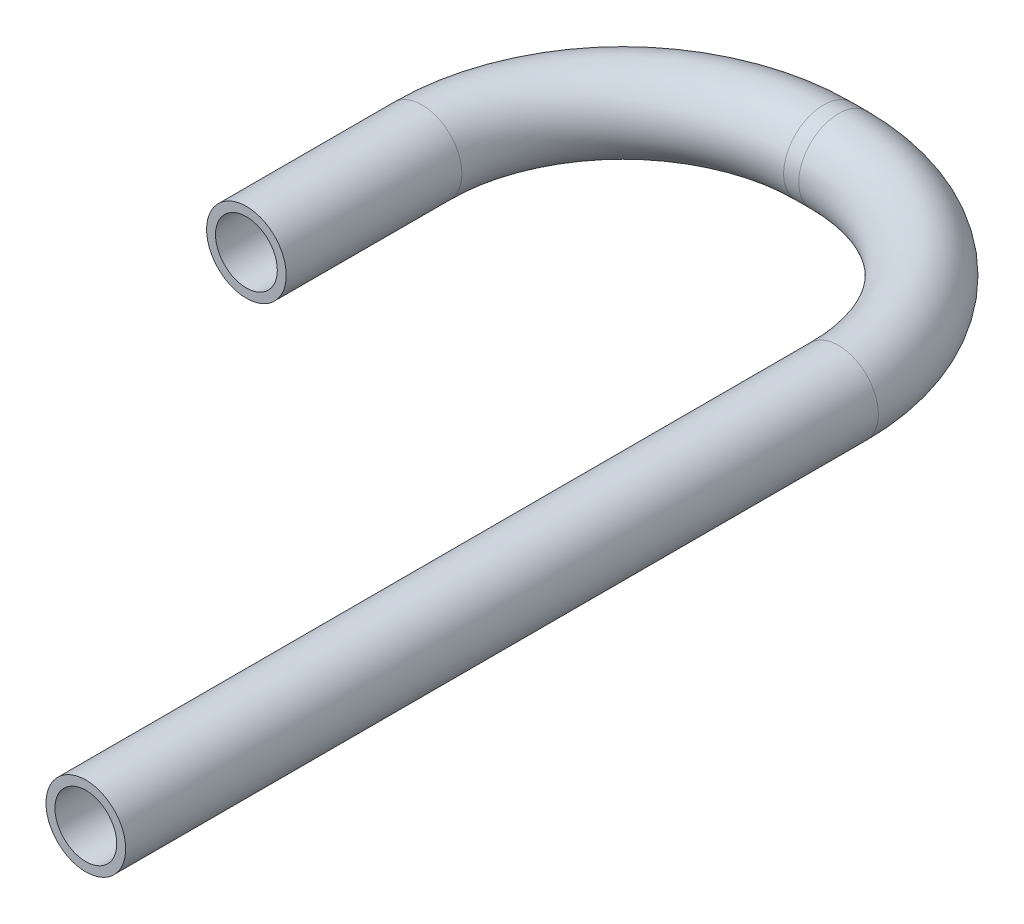
SolidWorks part; units mm, degrees
ref_plane "Front Plane" through (0, 0, 0) normal (0, 0, 1) x (1, 0, 0)
ref_plane "Top Plane" through (0, 0, 0) normal (0, 1, 0) x (1, 0, 0)
ref_plane "Right Plane" through (0, 0, 0) normal (1, 0, 0) x (0, 0, -1)
sketch "Sketch1" plane through (0, 0, 0) normal (0, 1, 0) x (1, 0, 0)
  line L0 (0, 0) -> (0, 14)
  line L1 (16, 30) -> (17.2, 30)
  line L2 (33.2, 14) -> (33.2, -46)
  arc A0 (17.2, 30) -> (33.2, 14) centre (17.2, 14) cw
  arc A1 (0, 14) -> (16, 30) centre (16, 14) cw
  dimension "D1" = 16
  dimension "D2" = 16
  dimension "D3" = 14
  dimension "D4" = 60
  dimension "D5" = 33.2
sketch "Sketch2" plane through (0, 0, 0) normal (0, 0, 1) x (1, 0, 0)
  circle A0 centre (0, 0) radius 3.175
  dimension "D1" = 6.35
sweep "Sweep-Thin1" add profiles "Sketch2" path "Sketch1" parameters "D1"=0.7112
